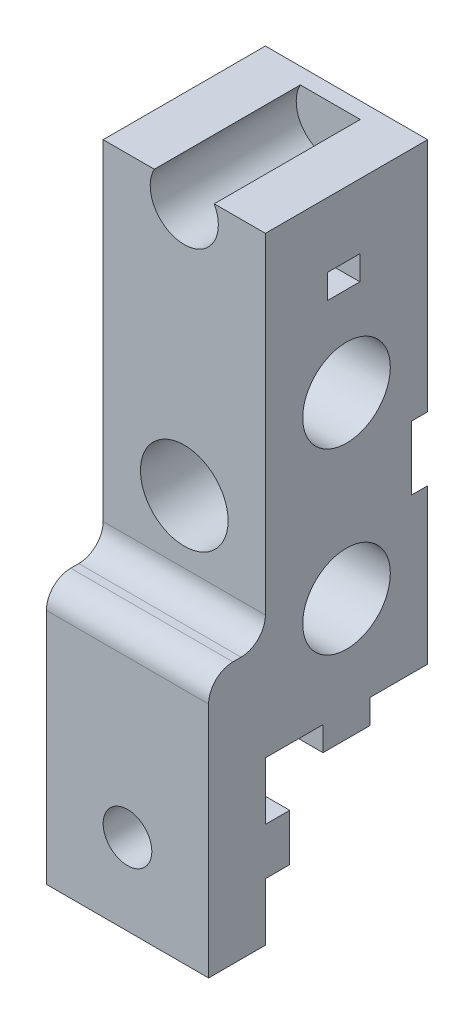
SolidWorks part; units mm, degrees
ref_plane "Front Plane" through (0, 0, 0) normal (0, 0, 1) x (1, 0, 0)
ref_plane "Top Plane" through (0, 0, 0) normal (0, 1, 0) x (1, 0, 0)
ref_plane "Right Plane" through (0, 0, 0) normal (1, 0, 0) x (0, 0, -1)
sketch "Sketch24" plane through (0, 0, 0) normal (1, 0, 0) x (0, 0, -1)
  line L0 (10, -9.1579) -> (10, 46.8421)
  line L1 (2.9, -9.1579) -> (2.9, -12.1579)
  line L2 (-10, 46.8421) -> (-10, -9.1579)
  line L3 (-10, -9.1579) -> (-2.9, -9.1579)
  line L4 (2.9, -12.1579) -> (-2.9, -12.1579)
  line L5 (-2.9, -12.1579) -> (-2.9, -9.1579)
  line L6 (2.9, -9.1579) -> (10, -9.1579)
  line L7 (-10, 46.8421) -> (10, 46.8421)
  line L9 (-2.3533, 38.8421) -> (1.6467, 38.8421)
  line L10 (-2.3533, 38.8421) -> (-2.3533, 35.8421)
  line L11 (-2.3533, 35.8421) -> (1.6467, 35.8421)
  line L12 (1.6467, 38.8421) -> (1.6467, 35.8421)
  line L13 (-2.3533, 38.8421) -> (1.6467, 35.8421) construction
  line L14 (-2.3533, 35.8421) -> (1.6467, 38.8421) construction
  circle A0 centre (0, 24.8421) radius 5.4
  circle A1 centre (0, 2.8421) radius 5.4
  point P2 (-0.3533, 37.3421)
  dimension "D6" = 10.8
  dimension "D1" = 22
  dimension "D2" = 5.8
  dimension "D3" = 3
  dimension "D4" = 7.1
  dimension "D5" = 56
  dimension "D7" = 9.5
  dimension "D8" = 12
extrude "Boss-Extrude1" add sketch "Sketch24" along normal blind 20
sketch "Sketch28" plane through (20, 0, 0) normal (1, 0, 0) x (0, 0, -1)
  line L3 (-10, 3.0921) -> (-10, -29.1579)
  line L4 (-10, 3.0921) -> (-17, 3.0921)
  line L5 (-10, 46.8421) -> (-10, -9.1579) construction
  line L6 (-17, 3.0921) -> (-17, -29.1579)
  line L7 (-17, -29.1579) -> (-10, -29.1579)
extrude "Boss-Extrude2" add sketch "Sketch28" against normal blind 20
sketch "Sketch25" plane through (0, 0, 10) normal (0, 0, 1) x (1, 0, 0)
  line L0 (20, -9.1579) -> (0, -9.1579) construction
  line L1 (0, 13.8421) -> (20, 13.8421) construction
  line L2 (0, 46.8421) -> (0, 3.0921) construction
  line L3 (20, 46.8421) -> (20, 3.0921) construction
  circle A0 centre (10, 13.8421) radius 5.4
  point P10 (10, 13.8421)
  dimension "D1" = 10.8
  dimension "D2" = 23
sketch "Sketch26" plane through (0, 0, 10) normal (0, 0, 1) x (1, 0, 0)
  line L0 (20, -9.1579) -> (0, -9.1579) construction
  line L1 (0, 44.8421) -> (20, 44.8421) construction
  line L2 (0, 46.8421) -> (0, 3.0921) construction
  line L3 (20, 46.8421) -> (20, 3.0921) construction
  circle A0 centre (10, 44.8421) radius 4.2
  point P11 (10, 44.8421)
  dimension "D2" = 8.4
  dimension "D1" = 54
extrude "Cut-Extrude1" cut sketch "Sketch25" against normal blind 20
extrude "Cut-Extrude2" cut sketch "Sketch26" against normal blind 18
sketch "Sketch27" plane through (0, 0, -10) normal (0, 0, -1) x (-1, 0, 0)
  circle A0 centre (-10, 13.8421) radius 10.75
extrude "Cut-Extrude3" cut sketch "Sketch27" against normal blind 2
fillet "Fillet4" radius 3 1 edges at (10, 3.0921, 17) type face fillet first side face at (7.5, 3.0921, 11.75) second side face at (10, -13.0329, 17)
fillet "Fillet6" radius 3 1 edges type face fillet first side face at (7.5, 3.0921, 11) second side face at (15.4, 13.8421, 10)
sketch "Sketch31" plane through (0, 0, 17) normal (0, 0, 1) x (1, 0, 0)
  line L0 (0, -29.1579) -> (20, -29.1579) construction
  circle A0 centre (10, -19.1579) radius 3
  dimension "D1" = 10
extrude "Cut-Extrude5" cut sketch "Sketch31" against normal blind 7
sketch "Sketch32" plane through (0, 0, 10) normal (0, 0, -1) x (-1, 0, 0)
  line L0 (0, -29.1579) -> (0, -9.1579) construction
  line L7 (-3, -16.2579) -> (0, -16.2579)
  line L8 (-3, -16.2579) -> (-3, -22.0579)
  line L9 (-3, -22.0579) -> (0, -22.0579)
  line L10 (0, -16.2579) -> (0, -22.0579)
  line L11 (-3, -16.2579) -> (0, -22.0579) construction
  line L12 (-3, -22.0579) -> (0, -16.2579) construction
  line L13 (-20, -29.1579) -> (-20, -9.1579) construction
  line L14 (-17, -16.2579) -> (-20, -16.2579)
  line L15 (-17, -16.2579) -> (-17, -22.0579)
  line L16 (-17, -22.0579) -> (-20, -22.0579)
  line L17 (-20, -16.2579) -> (-20, -22.0579)
  line L18 (-17, -16.2579) -> (-20, -22.0579) construction
  line L19 (-17, -22.0579) -> (-20, -16.2579) construction
  line L20 (-20, -19.1579) -> (0, -19.1579) construction
  point P1 (-1.5, -19.1579)
  point P16 (-18.5, -19.1579)
  dimension "D1" = 3
  dimension "D2" = 5.8
extrude "Boss-Extrude3" add sketch "Sketch32" along normal blind 3
